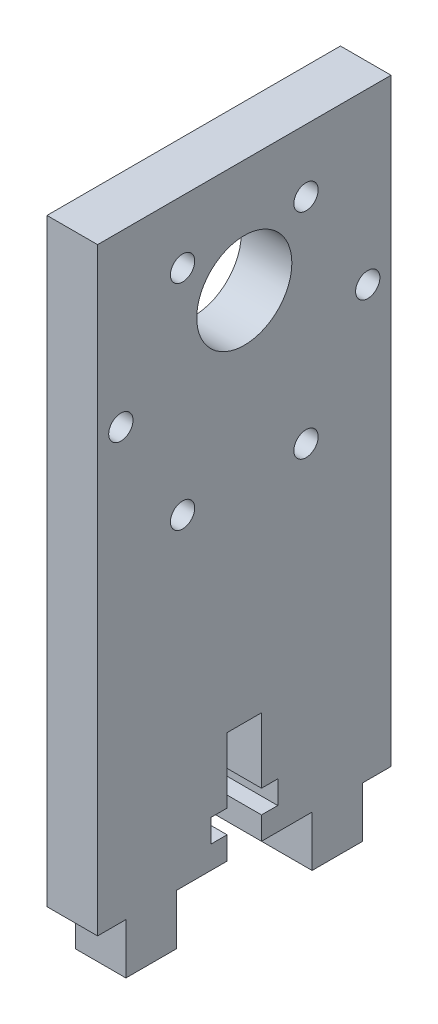
SolidWorks part; units mm, degrees
ref_plane "Front Plane" through (0, 0, 0) normal (0, 0, 1) x (1, 0, 0)
ref_plane "Top Plane" through (0, 0, 0) normal (0, 1, 0) x (1, 0, 0)
ref_plane "Right Plane" through (0, 0, 0) normal (1, 0, 0) x (0, 0, -1)
sketch "Motor plate" plane through (0, 0, 0) normal (1, 0, 0) x (0, 0, -1)
  line L0 (0, 16.2779) -> (7.747, 29.6961) construction
  line L1 (-18.415, -37.5701) -> (-14.859, -37.5701)
  line L2 (-18.415, -37.5701) -> (-18.415, 37.5701)
  line L3 (-18.415, 37.5701) -> (18.415, 37.5701)
  line L4 (18.415, -37.5701) -> (18.415, 37.5701)
  line L5 (-18.415, -37.5701) -> (18.415, 37.5701) construction
  line L6 (-18.415, 37.5701) -> (18.415, -37.5701) construction
  line L7 (14.859, -37.5701) -> (18.415, -37.5701)
  line L13 (0, 37.5701) -> (0, -24.5526) construction
  circle A0 centre (7.747, 29.6961) radius 1.524
  circle A1 centre (15.494, 16.2779) radius 1.524
  circle A2 centre (7.747, 2.8597) radius 1.524
  circle A3 centre (-7.747, 2.8597) radius 1.524
  circle A4 centre (-15.494, 16.2779) radius 1.524
  circle A5 centre (-7.747, 29.6961) radius 1.524
  circle A6 centre (0, 23.3899) radius 5.969
  circle A7 centre (0, 16.2779) radius 18.415 construction
  point P0 (0, 0)
  point P13 (0, -2.1371)
  point P15 (0, 16.2779)
  point P32 (0, 16.2779)
  line B0 (-8.509, -37.5701) -> (-8.509, -43.9201)
  line B1 (-8.509, -43.9201) -> (-14.859, -43.9201)
  line B2 (-14.859, -43.9201) -> (-14.859, -37.5701)
  line B3 (-2.159, -37.5701) -> (-2.159, -34.7024)
  line B4 (-2.159, -34.7024) -> (-4.2, -34.7024)
  line B5 (-4.2, -34.7024) -> (-4.2, -31.8024)
  line B6 (-4.2, -31.8024) -> (-2.159, -31.8024)
  line B7 (-2.159, -31.8024) -> (-2.159, -23.6001)
  line B8 (-2.159, -23.6001) -> (2.159, -23.6001)
  line B9 (2.159, -23.6001) -> (2.159, -31.8024)
  line B10 (2.159, -31.8024) -> (4.2, -31.8024)
  line B11 (4.2, -31.8024) -> (4.2, -34.7024)
  line B12 (4.2, -34.7024) -> (2.159, -34.7024)
  line B13 (2.159, -34.7024) -> (2.159, -37.5701)
  line B14 (0, -23.6001) -> (0, -37.5701) construction
  line B15 (8.509, -37.5701) -> (2.159, -37.5701)
  line B16 (14.859, -43.9201) -> (14.859, -37.5701)
  line B17 (-8.509, -37.5701) -> (-2.159, -37.5701)
  line B18 (8.509, -43.9201) -> (14.859, -43.9201)
  line B19 (8.509, -37.5701) -> (8.509, -43.9201)
  dimension "D3" = 30
  dimension "D4" = 15.494
  dimension "D5" = 3.048
  dimension "D8" = 11.938
  dimension "D2" = 36.83
  dimension "D1" = 60.96
  dimension "D6" = 6.35
  dimension "D7" = 6
  dimension "D9" = 7.112
sketch_block_instance "Male T-slot assembly-1"
sketch_block "Male T-slot assembly" parameters "D1"=6.35, "D2"=6.35, "D3"=4.318, "D4"=2.9, "D5"=8.4, "D6"=13.97, "D7"=6.35
extrude "Boss-Extrude1" add sketch "Motor plate" along normal blind 6.35 contours L3 | L4 L3 L2 A6 A5 A4 A3 A2 A1 A0 region at (0, -1.6709, 0)
equation "\"Ball Diameter\"= 1.75in"
equation "\"Sheet Thickness\"= 0.25in"
equation "\"Screw Diameter\"= .17in"
equation "\"Robot Diameter\"= 14in"
equation "\"Castor Screw Diameter\"= 0.22in"
equation "\"Wheel Diameter\" = 4in"
equation "\"Nut Diameter\" = 8.4mm"
equation "\"Nut Height\" = 2.9mm"
equation "\"Screw Height\" = 0.55in"
equation "\"D1@Boss-Extrude1\"=\"Sheet Thickness\""
equation "\"Ball Radius\" = \"Ball Diameter\"/2"
equation "\"Pulley Diameter\" = 1in"
equation "\"Reactor Height\" = 14in"
equation "\"Elevator Height\" = 11.5in"
equation "\"Elevator Width\" = \"Ball Diameter\" + 0.25in"
equation "\"Elevator Bearing Diameter\" = sqr(2*(\"Sheet Thickness\"^2)) + 0.2in"
equation "\"Elevator Axle Endcap Diameter\" = \"Pulley Diameter\" + 0.25in"
equation "\"Elevator Axle Length\" = \"Elevator Width\" + 8*\"Sheet Thickness\""
equation "\"Elevator Clearance from Axis\" = 3.5in"
equation "\"Elevator Horizontal Clearance\" = \"Elevator Width\" + 0.5in"
equation "\"Claw Horizontal Seperation\" = (\"Elevator Width\"/2) - (1.5 * \"Sheet Thickness\") - 0.15in"
equation "\"Claw Radius\" = \"Ball Radius\" + 0.1in"
equation "\"Castor Wheel Height\" = 1.25in"
equation "\"D10@Motor plate\"=\"Pulley Diameter\""
